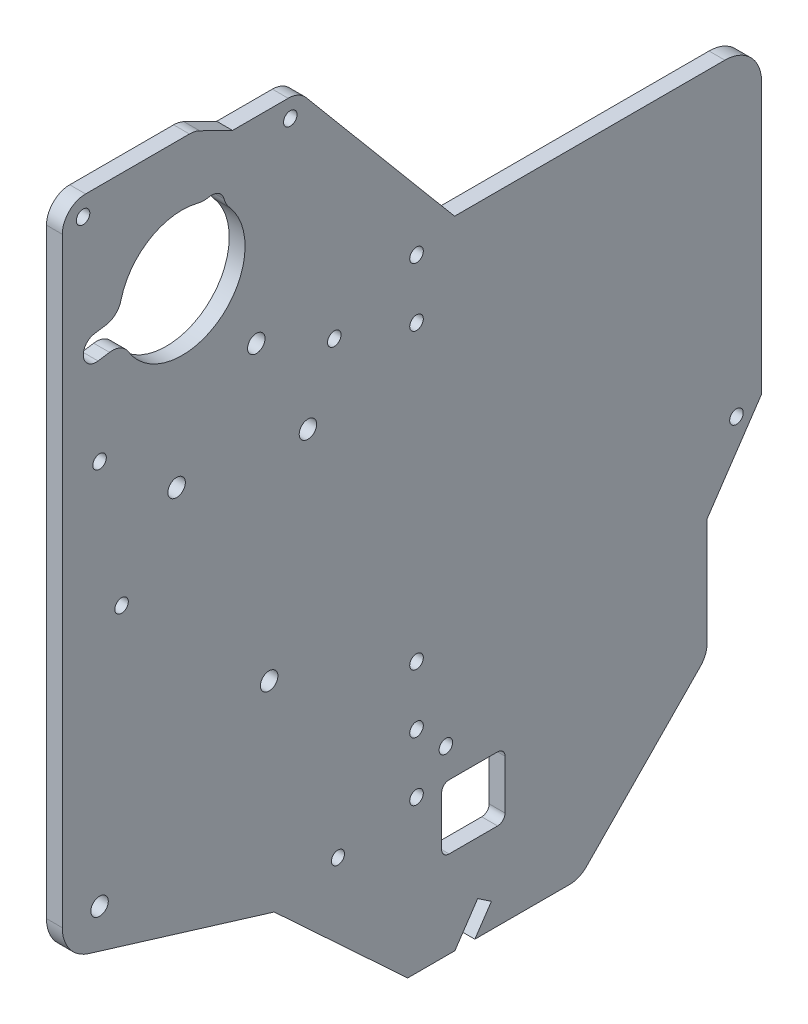
SolidWorks part; units mm, degrees
material "Acrylic (Medium-high impact)"
ref_plane "Front" through (0, 0, 0) normal (0, 0, 1) x (1, 0, 0)
ref_plane "Top" through (0, 0, 0) normal (0, 1, 0) x (1, 0, 0)
ref_plane "Right" through (0, 0, 0) normal (1, 0, 0) x (0, 0, -1)
ref_axis "side-side" through (80.9, 0, 0) along (-1, 0, 0)
ref_axis "up-down" through (0, 50, 0) along (0, -1, 0)
ref_axis "front-back" through (0, 0, -80.9) along (0, 0, 1)
sketch "Sketch1" plane through (0, 0, 0) normal (1, 0, 0) x (0, 0, -1)
  line L1 (-114.2854, 109.5191) -> (-221.6238, -49.6166)
  line L3 (-114.2854, 109.5191) -> (-110.9692, 107.2824)
  line L5 (-218.3076, -51.8533) -> (-110.9692, 107.2824)
  line L10 (-277.2593, 32) -> (-277.2593, 30)
  line L11 (133.7407, 32) -> (-277.2593, 32)
  line L12 (133.7407, 30) -> (133.7407, 32)
  line L13 (-277.2593, 30) -> (133.7407, 30)
  line L18 (-277.2593, 2) -> (-277.2593, 0)
  line L19 (133.7407, 2) -> (-277.2593, 2)
  line L20 (133.7407, 0) -> (133.7407, 2)
  line L21 (-277.2593, 0) -> (133.7407, 0)
  line L23 (-119.7593, 64) -> (-117.7593, 64)
  line L25 (-87.7593, 64) -> (-89.7593, 64)
  line L38 (-117.2593, 32) -> (-90.2593, 32)
  line L39 (-87.7593, 34.5) -> (-87.7593, 61.5)
  line L40 (-87.7593, 61.5) -> (-89.7593, 61.5)
  line L41 (-89.7593, 61.5) -> (-89.7593, 34)
  line L42 (-89.7593, 34) -> (-117.7593, 34)
  line L43 (-117.7593, 34) -> (-117.7593, 61.5)
  line L44 (-117.7593, 61.5) -> (-119.7593, 61.5)
  line L45 (-119.7593, 61.5) -> (-119.7593, 34.5)
  circle A1 centre (-286.3713, 57.4304) radius 2.3813
  circle A3 centre (-229.5573, 141.6606) radius 2.3813
  circle A5 centre (-141.6718, 148.4823) radius 47.625
  arc A8 (-90.2593, 32) -> (-87.7593, 34.5) centre (-90.2593, 34.5) ccw
  arc A9 (-119.7593, 34.5) -> (-117.2593, 32) centre (-117.2593, 34.5) ccw
sketch "Sketch3" plane through (0, 0, 0) normal (1, 0, 0) x (0, 0, -1)
  line L1 (-247.956, 231.9223) -> (-247.956, 224)
  line L3 (-218.456, 224) -> (-247.956, 224)
  line L5 (-215.956, 224) -> (-184.6269, 224)
  line L6 (-215.956, 224) -> (-215.956, 190.282)
  line L7 (-215.956, 190.282) -> (-184.6269, 190.282)
  line L8 (-184.6269, 224) -> (-184.6269, 190.282)
  circle A1 centre (-240.1331, 87.5182) radius 4
  circle A3 centre (-265.3667, 145.7893) radius 4
  circle A4 centre (-243.6293, 168.9312) radius 4
  circle A5 centre (-263.8726, 193.3908) radius 6
  circle A7 centre (-279.1322, 191.0684) radius 1.5
  circle A9 centre (-255.7992, 206.5464) radius 1.5
  circle A11 centre (-263.8726, 193.3908) radius 11
  circle A16 centre (-222.3713, 159.4304) radius 1.778
  circle A17 centre (-286.3713, 162.4304) radius 1.778
  circle A18 centre (-234.3713, 217.4304) radius 1.778
  circle A19 centre (-290.8713, 222.4304) radius 1.778
  arc A21 (-277.1812, 223.3695) -> (-292.7489, 177.8345) centre (-263.8726, 193.3908) ccw
  circle A23 centre (-280.3713, 125.4304) radius 1.778
  circle A25 centre (-221.3713, 36.4304) radius 1.778
sketch "Sketch2" plane through (0, 0, 0) normal (1, 0, 0) x (0, 0, -1)
  line L0 (-115.8892, 171.954) -> (-189.5806, 171.954)
  line L1 (133.7407, 32) -> (-277.2593, 32) construction
  line L2 (-228.2267, 167.3369) -> (-294.9337, 62.8994) construction
  line L3 (-289.341, 47.7141) -> (-238.7597, 32.254)
  line L4 (-277.2593, 0) -> (133.7407, 0) construction
  line L5 (-238.7597, 32.254) -> (-105.8892, 32.254) construction
  line L6 (-277.2593, 30) -> (133.7407, 30) construction
  line L7 (133.7407, 2) -> (-277.2593, 2) construction
  line L8 (-277.2593, 32) -> (-277.2593, 30) construction
  line L9 (-105.8892, 88.0777) -> (-105.8892, 161.954)
  line L10 (-158.1882, 29.746) -> (-277.2593, 29.746) construction
  line L11 (-158.1882, 29.746) -> (-158.1882, 2.254) construction
  line L12 (-158.1882, 2.254) -> (-277.2593, 2.254) construction
  line L13 (-277.2593, 29.746) -> (-277.2593, 2.254) construction
  line L14 (-114.2854, 109.5191) -> (-221.6238, -49.6166) construction
  line L15 (-218.3076, -51.8533) -> (-110.9692, 107.2824) construction
  line L16 (-238.7597, 32.254) -> (-202.3597, -1.524)
  line L17 (-202.3597, -1.524) -> (-189.4913, -1.524)
  line L18 (-119.7593, 61.5) -> (-119.7593, 34.5) construction
  line L19 (-120.7593, 66.032) -> (-105.8892, 66.032) construction
  line L20 (-287.8294, 193.2851) -> (-284.7019, 193.761)
  line L21 (-120.7593, 36.576) -> (-120.7593, 66.032)
  line L22 (-119.7593, 64) -> (-117.7593, 64) construction
  line L23 (-183.2787, 7.6866) -> (-189.4913, -1.524)
  line L24 (-183.2787, 7.6866) -> (-179.5414, 5.1658)
  line L25 (-120.7593, 66.032) -> (-105.8892, 88.0777)
  line L26 (-189.5806, 171.954) -> (-230.0702, 220.2077)
  line L27 (-184.0537, -1.524) -> (-158.1882, -1.524)
  line L28 (-179.5414, 5.1658) -> (-184.0537, -1.524)
  line L29 (-234.9346, 222.476) -> (-250.1193, 222.476)
  line L30 (-218.456, 224) -> (-247.956, 224) construction
  line L31 (-250.1193, 222.476) -> (-259.0691, 226.8624)
  line L32 (-261.8637, 227.5104) -> (-290.1813, 227.5104)
  line L33 (-296.5313, 57.4304) -> (-296.5313, 221.1604)
  line L36 (-263.8726, 193.3908) -> (-255.7992, 206.5464) construction
  line L37 (-286.7762, 186.3647) -> (-283.6486, 186.8407)
  line L38 (-279.1322, 191.0684) -> (-263.8726, 193.3908) construction
  line L40 (-177.86, 39.62) -> (-191.068, 39.62)
  line L41 (-175.828, 37.588) -> (-175.828, 24.158)
  line L42 (-177.86, 22.126) -> (-191.068, 22.126)
  line L43 (-193.1, 37.588) -> (-193.1, 24.158)
  line L45 (-122.5714, 32.1341) -> (-153.6503, 0.3841)
  arc A0 (-296.5313, 57.4304) -> (-289.341, 47.7141) centre (-286.3713, 57.4304) ccw
  circle A1 centre (-243.6293, 168.9312) radius 2.3813
  circle A2 centre (-286.3713, 57.4304) radius 2.3813
  circle A3 centre (-229.5573, 141.6606) radius 2.3813 construction
  circle A4 centre (-229.5573, 141.6606) radius 2.3813
  arc A5 (-120.7593, 36.576) -> (-158.1882, -1.524) centre (-120.0821, -1.524) ccw construction
  arc A6 (-105.8892, 161.954) -> (-115.8892, 171.954) centre (-115.8892, 161.954) ccw
  arc A7 (-228.2267, 167.3369) -> (-219.7991, 171.954) centre (-219.7991, 161.954) cw construction
  circle A8 centre (-290.8713, 222.4304) radius 1.778 construction
  circle A9 centre (-112.7323, 86.2169) radius 1.85
  circle A10 centre (-234.3713, 217.4304) radius 1.778 construction
  arc A11 (-290.1813, 227.5104) -> (-296.5313, 221.1604) centre (-290.1813, 221.1604) ccw
  arc A12 (-259.0691, 226.8624) -> (-261.8637, 227.5104) centre (-261.8637, 221.1604) ccw
  circle A13 centre (-199.956, 72) radius 1.85
  circle A14 centre (-199.956, 152) radius 1.85
  circle A15 centre (-199.956, 168) radius 1.85
  arc A16 (-230.0702, 220.2077) -> (-234.9346, 222.476) centre (-234.9346, 216.126) ccw
  circle A17 centre (-221.3713, 36.4304) radius 1.778
  circle A18 centre (-240.1331, 87.5182) radius 2.3813
  circle A19 centre (-199.956, 40) radius 1.85
  circle A20 centre (-191.956, 48) radius 1.85
  circle A21 centre (-199.956, 56) radius 1.85
  circle A22 centre (-280.3713, 125.4304) radius 1.8415
  circle A23 centre (-222.3713, 159.4304) radius 1.8415
  circle A24 centre (-286.3713, 162.4304) radius 1.8415
  arc A25 (-252.4172, 207.4476) -> (-256.5272, 209.9699) centre (-255.7992, 206.5464) ccw
  circle A26 centre (-265.3667, 145.7893) radius 2.3813
  arc A27 (-287.8294, 193.2851) -> (-286.7762, 186.3647) centre (-287.3028, 189.8249) ccw
  circle A28 centre (-263.8726, 193.3908) radius 6 construction
  arc A29 (-175.828, 24.158) -> (-177.86, 22.126) centre (-177.86, 24.158) cw
  circle A30 centre (-234.3713, 217.4304) radius 1.8415
  circle A31 centre (-290.8713, 222.4304) radius 1.8415
  arc A32 (-256.5272, 209.9699) -> (-259.6197, 210.0327) centre (-257.9391, 216.6088) cw
  arc A33 (-191.068, 22.126) -> (-193.1, 24.158) centre (-191.068, 24.158) cw
  arc A34 (-278.545, 184.4599) -> (-250.9607, 204.7189) centre (-263.8726, 193.3908) ccw
  arc A35 (-252.4172, 207.4476) -> (-250.9607, 204.7189) centre (-245.8586, 209.1952) ccw
  circle A36 centre (-263.8726, 193.3908) radius 11 construction
  arc A37 (-259.6197, 210.0327) -> (-280.5376, 197.5524) centre (-263.8726, 193.3908) ccw
  arc A38 (-278.545, 184.4599) -> (-283.6486, 186.8407) centre (-282.8843, 181.8186) ccw
  arc A39 (-280.5376, 197.5524) -> (-284.7019, 193.761) centre (-285.4662, 198.7832) cw
  arc A40 (-191.068, 39.62) -> (-193.1, 37.588) centre (-191.068, 37.588) ccw
  arc A41 (-177.86, 39.62) -> (-175.828, 37.588) centre (-177.86, 37.588) cw
  arc A42 (-120.7593, 36.576) -> (-122.5714, 32.1341) centre (-127.1093, 36.576) cw
  arc A43 (-158.1882, -1.524) -> (-153.6503, 0.3841) centre (-158.1882, 4.826) ccw
  point P28 (-163.2682, 29.746)
  point P45 (-277.2593, 31)
  point P84 (-260.3913, 227.5104)
  point P108 (-290.7629, 189.2983)
  point P143 (-193.1, 30.873)
  dimension "D1" = 10.16
  dimension "D14" = 10
  dimension "D15" = 22.0457
  dimension "D23" = 5.08
  dimension "D24" = 5.0456
  dimension "D25" = 15.748
  dimension "D26" = 30.48
  dimension "D27" = 5.66
  dimension "D28" = 6.35
  dimension "D29" = 6.35
  dimension "D30" = 3.556
  dimension "D31" = 4.7625
  dimension "D32" = 4.7625
  dimension "D33" = 3.683
  dimension "D34" = 7
  dimension "D37" = 5.08
  dimension "D35" = 34.3535
  dimension "D40" = 2.032
  dimension "D45" = 6.35
  dimension "D39" = 6.856
  dimension "D2" = 139.7
  dimension "D3" = 5.08
  dimension "D4" = 0.254
  dimension "D5" = 0.254
  dimension "D6" = 0.254
  dimension "D7" = 5.08
  dimension "D8" = 12.7
  dimension "D9" = 36.4
  dimension "D10" = 1.524
  dimension "D12" = 2.032
  dimension "D13" = 38.1
  dimension "D16" = 0.254
  dimension "D17" = 0.254
  dimension "D11" = 1
  dimension "D18" = 4.508
  dimension "D19" = 74.8996
  dimension "D20" = 5.08
  dimension "D21" = 50
  dimension "D22" = 1.524
  dimension "D36" = 12.7
  dimension "D38" = 3.5
  dimension "D41" = 7.62
  dimension "D42" = 17.272
  dimension "D44" = 17.494
extrude "Boss-Extrude1" add sketch "Sketch2" along normal blind 4.318
